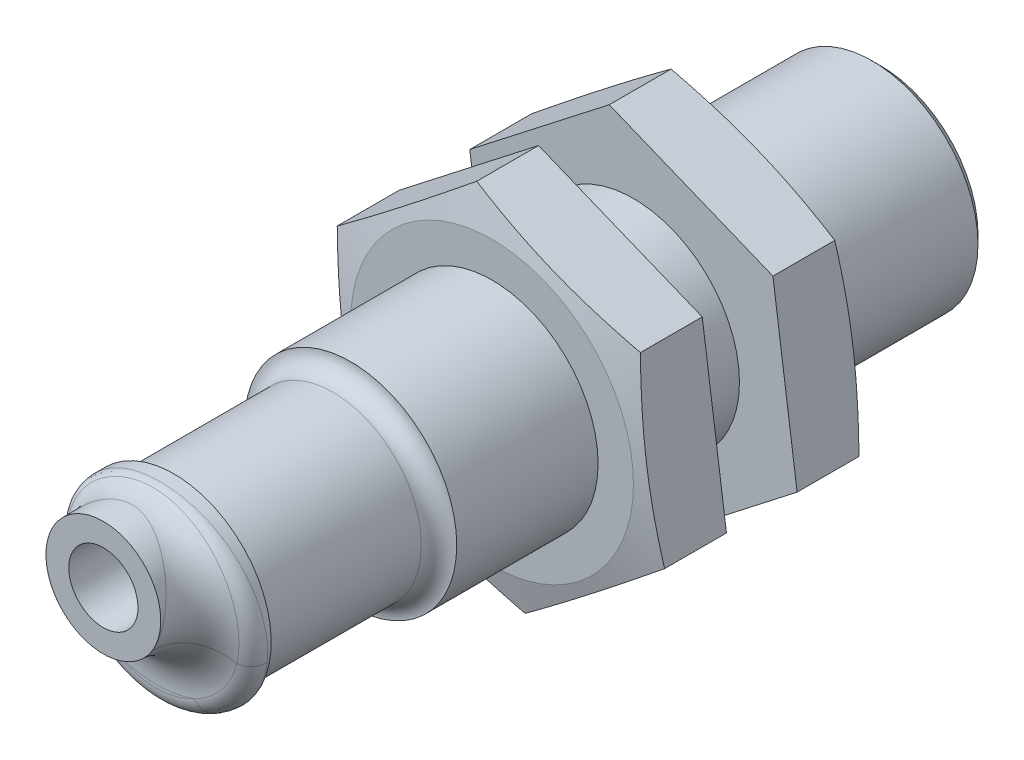
SolidWorks part; units mm, degrees
ref_plane "Plano frontal" through (0, 0, 0) normal (0, 0, 1) x (1, 0, 0)
ref_plane "Plano superior" through (0, 0, 0) normal (0, 1, 0) x (1, 0, 0)
ref_plane "Plano direito" through (0, 0, 0) normal (1, 0, 0) x (0, 0, -1)
sketch "Esboço1" plane through (0, 0, 0) normal (1, 0, 0) x (0, 0, -1)
  line L0 (0, 0) -> (60, 0) construction
  line L1 (21.5, 6) -> (38, 6)
  line L2 (0.8, 5) -> (0.8186, 4.8)
  line L3 (0, 0) -> (0, 5)
  line L4 (2.5, 6) -> (8, 6)
  line L5 (60, 0) -> (60, 5.5)
  line L6 (8, 6) -> (8, 5.5)
  line L7 (0, 5) -> (0.8, 5)
  line L8 (2.5, 6) -> (2.5, 5.5)
  line L9 (8.5, 5) -> (21, 5)
  line L10 (21.5, 6) -> (21.5, 5.5)
  line L11 (59.5, 6) -> (60, 5.5)
  line L12 (0, 0) -> (60, 0)
  line L13 (0.8186, 4.8) -> (0.8373, 5)
  line L14 (0.8, 5) -> (0.8373, 5) construction
  line L15 (0.8373, 5) -> (2, 5)
  line L16 (42, 6) -> (46, 6)
  line L17 (38.5, 10) -> (38, 8)
  line L18 (50, 6) -> (50, 8)
  line L19 (49.5, 10) -> (46, 10)
  line L20 (46, 6) -> (46, 10)
  line L21 (50, 6) -> (59.5, 6)
  line L22 (42, 6) -> (42, 10)
  line L23 (42, 10) -> (38.5, 10)
  line L24 (38, 6) -> (38, 8)
  line L26 (50, 8) -> (49.5, 10)
  arc A0 (21, 5) -> (21.5, 5.5) centre (21, 5.5) ccw
  arc A1 (8, 5.5) -> (8.5, 5) centre (8.5, 5.5) ccw
  arc A2 (2, 5) -> (2.5, 5.5) centre (2, 5.5) ccw
  point P2 (60, 6)
  point P6 (0, 5)
  point P12 (21.5, 5)
  point P15 (8, 5)
  point P18 (2.5, 5)
  point P20 (0.8, 5)
  point P23 (0.8186, 4.8)
  point P27 (0.8186, 5)
  point P30 (46, 10)
  point P31 (50, 10)
  point P34 (38, 10)
  point P35 (42, 10)
  dimension "D1" = 5.5
  dimension "D3" = 13.5
  dimension "D7" = 0.5
  dimension "D2" = 60
  dimension "D4" = 6
  dimension "D5" = 1
  dimension "D8" = 0.8
  dimension "D9" = 0.2
  dimension "D10" = 10
  dimension "D6" = 2.5
  dimension "D12" = 4
  dimension "D13" = 4
  dimension "D14" = 4
  dimension "D15" = 0.5
  dimension "D16" = 4
  dimension "D19" = 2
  dimension "D20" = 0.5
revolve "Revolução1" add sketch "Esboço1" angle 360 about L0
sketch "Esboço2" plane through (0, 0, 0) normal (0, 0, 1) x (1, 0, 0)
  circle A0 centre (0, 0) radius 4
  circle A1 centre (0, 0) radius 5 construction
  dimension "D1" = 1
extrude "Corte-extrusão1" cut sketch "Esboço2" against normal blind 10
sketch "Esboço5" plane through (0, 0, -10) normal (0, 0, 1) x (1, 0, 0)
  circle A0 centre (0, 2) radius 0.25
  dimension "D1" = 2
  dimension "D2" = 0.5
extrude "Ressalto-extrusão1" add sketch "Esboço5" along normal blind 10
fillet "Filete1" radius 0.2 1 edges at (0.25, 2, 0)
pattern_circular "PadrãoCircular1" count 4 over 360 about axis through (0, 0, 0) along (0, 0, 1) of "Ressalto-extrusão1", "Filete1"
sketch "Esboço10" plane through (0, 0, -50) normal (0, 0, -1) x (-1, 0, 0)
  line L1 (7.8935, -6.1394) -> (9.2636, 3.7663)
  line L2 (9.2636, 3.7663) -> (1.3701, 9.9057)
  line L3 (1.3701, 9.9057) -> (-7.8935, 6.1394)
  line L4 (-7.8935, 6.1394) -> (-9.2636, -3.7663)
  line L5 (-9.2636, -3.7663) -> (-1.3701, -9.9057)
  line L6 (-1.3701, -9.9057) -> (7.8935, -6.1394)
  circle A0 centre (0, 0) radius 8.6603 construction
extrude "Corte-extrusão2" cut sketch "Esboço10" against normal through all flip side to cut
sketch "Esboço11" plane through (0, 0, 0) normal (1, 0, 0) x (0, 0, -1)
  line L0 (60, -5.5) -> (60, 5.5) construction
  line L1 (-7.042, 7.4228) -> (30, 7.4228)
  line L2 (-7.042, 7.4228) -> (-7.042, -9.9451)
  line L3 (-7.042, -9.9451) -> (30, -9.9451)
  line L4 (30, 7.4228) -> (30, -9.9451)
  dimension "D1" = 30
extrude "Corte-extrusão3" cut sketch "Esboço11" against normal through all both and the other way through all
sketch "Esboço12" plane through (0, 0, -30) normal (0, 0, 1) x (1, 0, 0)
  circle A0 centre (0, 0) radius 5
  dimension "D1" = 10
extrude "Ressalto-extrusão2" add sketch "Esboço12" along normal blind 10
sketch "Esboço13" plane through (0, 0, -20) normal (0, 0, 1) x (1, 0, 0)
  circle A0 centre (0, 0) radius 5.5
extrude "Ressalto-extrusão3" add sketch "Esboço13" along normal blind 1
sketch "Esboço14" plane through (0, 0, -19) normal (0, 0, 1) x (1, 0, 0)
  circle A0 centre (0, 1.9216) radius 3.25
extrude "Ressalto-extrusão4" add sketch "Esboço14" along normal blind 3 contours A0
sketch "Esboço15" plane through (0, 0, -16) normal (0, 0, 1) x (1, 0, 0)
  circle A0 centre (0, 1.9216) radius 1.9593
  circle A1 centre (0, 1.9216) radius 3.25 construction
  dimension "D1" = 1.2907
extrude "Corte-extrusão4" cut sketch "Esboço15" against normal up to surface (3 mm away) up to face at (5.5, 0, -19)
fillet "Filete2" radius 3 1 edges at (3.25, 1.9216, -19)
fillet "Filete3" radius 1 2 edges at (0, 5.5, -19) (0, -5.5, -19)
fillet "Filete4" radius 1 1 edges at (-5, 0, -30)
equation "\"comprimento\"= \"RD1@Anotações\""
